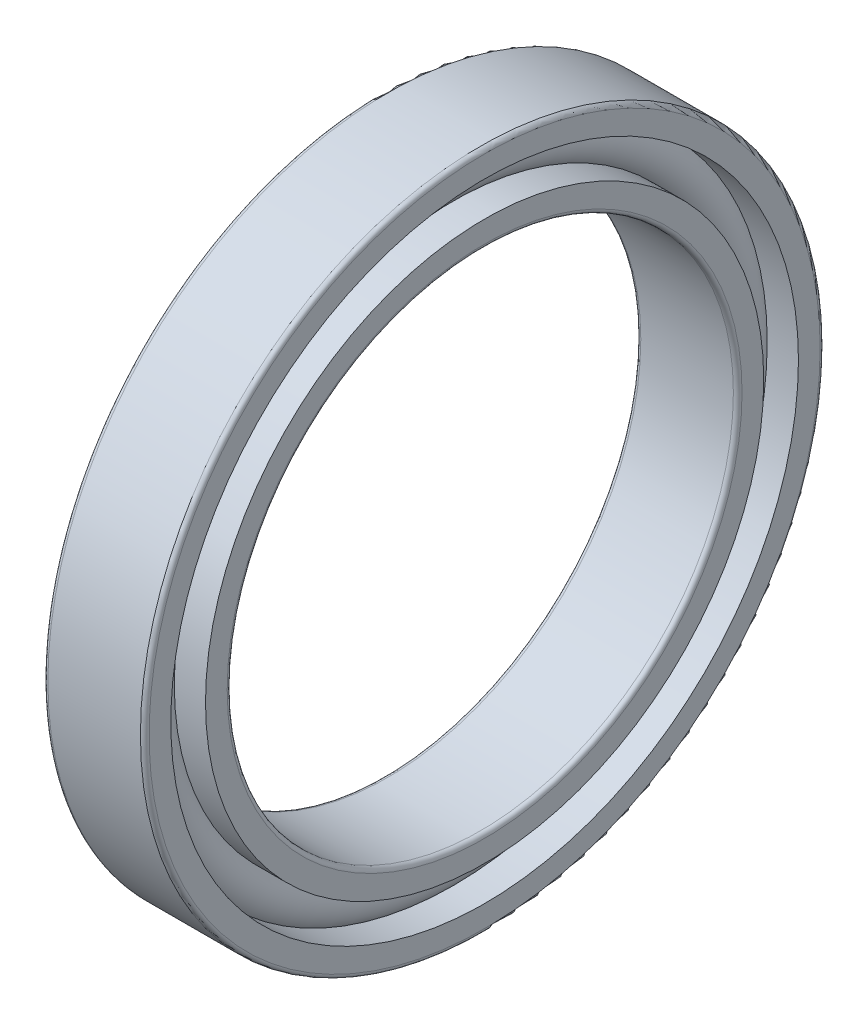
SolidWorks part; units mm, degrees
ref_plane "Plane1" through (0, 0, 0) normal (0, 0, 1) x (1, 0, 0)
ref_plane "Plane2" through (0, 0, 0) normal (0, 1, 0) x (1, 0, 0)
ref_plane "Plane3" through (0, 0, 0) normal (1, 0, 0) x (0, 0, -1)
sketch "Clipboard" plane through (0, 0, 0) normal (0, 0, 1) x (1, 0, 0)
  line L0 (-10, 0) -> (10, 0) construction
  line L1 (0, 0) -> (22.3471, -0.7804)
  line L2 (0, 0) -> (20.4875, 0.7154)
  line L3 (0, 0) -> (22.3471, -0.7804)
  line L4 (0, 0) -> (-22.3573, -0.3902)
  dimension "BallCLRad" = 20.5
sketch "CagSpiSke" plane through (0, 0, 0) normal (0, 0, 1) x (1, 0, 0)
  line L0 (0.18, 20.2) -> (0.18, 20.8)
  line L1 (0.18, 20.8) -> (-0.18, 20.8)
  line L2 (-0.18, 20.8) -> (-0.18, 20.2)
  line L3 (-0.18, 20.2) -> (0.18, 20.2)
  line L4 (-20.6375, 0) -> (20.6375, 0) construction
  line L5 (0, 0) -> (0, 23.7692) construction
  dimension "OD" = 41.6
  dimension "ID" = 40.4
revolve "CageSpine" add sketch "CagSpiSke" angle 0.001 about L4 reverse direction yes
ref_axis "Axis1" through (-50, 0, 0) along (1, 0, 0)
sketch "CagBalSke" plane through (0, 0, 0) normal (0, 0, 1) x (1, 0, 0)
  line L0 (-1.98, 20.5) -> (1.98, 20.5)
  line L1 (-1.905, 20.5) -> (1.905, 20.5) construction
  line L2 (-10, 0) -> (10, 0) construction
  line L3 (0, 0) -> (0, 24) construction
  arc A0 (1.98, 20.5) -> (-1.98, 20.5) centre (0, 20.5) cw
  dimension "BallCLRad" = 20.5
revolve "CageBall" [suppressed] add sketch "CagBalSke" angle 360 about L1 reverse direction yes
pattern_circular "CageBalls" [suppressed] count 2 every 180 about axis through (-50, 0, 0) along (1, 0, 0)
sketch "CagTrmODSke" plane through (0, 0, 0) normal (0, 0, 1) x (1, 0, 0)
  line L0 (1.981, 20.8) -> (1.981, 22.481)
  line L1 (1.981, 22.481) -> (-1.981, 22.481)
  line L2 (-1.981, 22.481) -> (-1.981, 20.8)
  line L3 (-1.981, 20.8) -> (1.981, 20.8)
  line L4 (-20.6375, 0) -> (20.6375, 0) construction
  line L5 (0, 0) -> (0, 25) construction
  dimension "Width" = 3.962
  dimension "ID" = 41.6
  dimension "OD" = 44.962
revolve "CageTrimOD" [suppressed] cut sketch "CagTrmODSke" angle 360 about L4 reverse direction yes
sketch "CagTrmIDSke" plane through (0, 0, 0) normal (0, 0, 1) x (1, 0, 0)
  line L0 (1.981, 18.521) -> (1.981, 20.2)
  line L1 (1.981, 20.2) -> (-1.981, 20.2)
  line L2 (-1.981, 20.2) -> (-1.981, 18.521)
  line L3 (-1.981, 18.521) -> (1.981, 18.521)
  line L4 (-20.6375, 0) -> (20.6375, 0) construction
  line L5 (0, 0) -> (0, 25) construction
  dimension "Width" = 3.962
  dimension "ID" = 37.042
  dimension "OD" = 40.4
revolve "CageTrimID" [suppressed] cut sketch "CagTrmIDSke" angle 360 about L4 reverse direction yes
sketch "BalSimSke" plane through (0, 0, 0) normal (0, 0, 1) x (1, 0, 0)
  line L0 (-10, 0) -> (10, 0) construction
  line L1 (-10, 20.5) -> (10, 20.5) construction
  line L2 (0, 0) -> (0, 23) construction
  circle A0 centre (0, 20.5) radius 1.8
  dimension "BallCLRad" = 20.5
  dimension "Ball_diameter" = 3.6
revolve "BallsSimplified" add sketch "BalSimSke" angle 360 about L0
sketch "BalDetSke" plane through (0, 0, 0) normal (0, 0, 1) x (1, 0, 0)
  line L0 (-1.8, 20.5) -> (1.8, 20.5)
  line L1 (-1.905, 20.5) -> (1.905, 20.5) construction
  line L2 (0, 0) -> (0, 25) construction
  arc A0 (1.8, 20.5) -> (-1.8, 20.5) centre (0, 20.5) cw
  dimension "BallCLRad" = 20.5
  dimension "Ball_diameter" = 3.6
revolve "BallDetailed" [suppressed] add sketch "BalDetSke" angle 360 about L1 reverse direction yes
sketch "InnRacSke" plane through (0, 0, 0) normal (0, 0, 1) x (1, 0, 0)
  line L0 (-1.3079, 19.3) -> (-3.5, 19.3)
  line L1 (-3.5, 19.3) -> (-3.5, 17.8)
  line L2 (-3.2, 17.5) -> (3.2, 17.5)
  line L3 (3.5, 17.8) -> (3.5, 19.3)
  line L4 (3.5, 19.3) -> (1.3079, 19.3)
  line L5 (-20.6375, 0) -> (20.6375, 0) construction
  line L6 (0, 0) -> (0, 30) construction
  arc A0 (-3.5, 17.8) -> (-3.2, 17.5) centre (-3.2, 17.8) ccw
  arc A1 (3.2, 17.5) -> (3.5, 17.8) centre (3.2, 17.8) ccw
  arc A2 (1.3079, 19.3) -> (-1.3079, 19.3) centre (0, 20.5) cw
  dimension "BallCLRad" = 20.5
  dimension "Fillet_radius" = 0.3
  dimension "Ball_diameter" = 3.55
  dimension "ID" = 35
  dimension "OD" = 38.6
  dimension "Width" = 7
revolve "InnerRace" add sketch "InnRacSke" angle 360 about L5 reverse direction yes
sketch "OutRacSke" plane through (0, 0, 0) normal (0, 0, 1) x (1, 0, 0)
  line L0 (-1.3079, 21.7) -> (-3.5, 21.7)
  line L1 (-3.5, 21.7) -> (-3.5, 23.2)
  line L2 (-3.2, 23.5) -> (3.2, 23.5)
  line L3 (3.5, 23.2) -> (3.5, 21.7)
  line L4 (3.5, 21.7) -> (1.3079, 21.7)
  line L5 (-20.6375, 0) -> (20.6375, 0) construction
  line L6 (0, 0) -> (0, 30) construction
  arc A0 (-3.5, 23.2) -> (-3.2, 23.5) centre (-3.2, 23.2) cw
  arc A1 (3.2, 23.5) -> (3.5, 23.2) centre (3.2, 23.2) cw
  arc A2 (1.3079, 21.7) -> (-1.3079, 21.7) centre (0, 20.5) ccw
  dimension "BallCLRad" = 20.5
  dimension "Fillet_radius" = 0.3
  dimension "Ball_diameter" = 3.55
  dimension "Width" = 7
revolve "OuterRace" add sketch "OutRacSke" angle 360 about L5 reverse direction yes
pattern_circular "BallsDetailed" [suppressed] count 2 every 180 about axis through (-50, 0, 0) along (1, 0, 0)
equation "\"BallCLRad@Clipboard\" = ( \"OD@OutRacSke\" + \"ID@InnRacSke\" ) / 4"
equation "\"BallCLRad@BalSimSke\" = \"BallCLRad@Clipboard\""
equation "\"BallCLRad@BalDetSke\" = \"BallCLRad@Clipboard\""
equation "\"BallCLRad@InnRacSke\" = \"BallCLRad@Clipboard\""
equation "\"BallCLRad@OutRacSke\" = \"BallCLRad@Clipboard\""
equation "\"Ball_diameter@InnRacSke\" = \"Ball_diameter@BalDetSke\" - 0.05"
equation "\"Ball_diameter@OutRacSke\" = \"Ball_diameter@BalDetSke\" - 0.05"
equation "\"Ball_diameter@BalSimSke\" = \"Ball_diameter@BalDetSke\""
equation "\"Width@OutRacSke\" = \"Width@InnRacSke\""
equation "\"Fillet_radius@OutRacSke\" = \"Fillet_radius@InnRacSke\""
equation "\"Max_count@Clipboard\" = int( 3.14159265 / atn(( \"Ball_diameter@BalDetSke\" / 2) / sqr( \"BallCLRad@Clipboard\"  *  \"BallCLRad@Clipboard\" - ( \"Ball_diameter@BalDetSke\" / 2) *  ( \"Ball_diameter@BalDetSke\" / 2))))"
equation "\"Max_count@Clipboard\" = ((sgn( \"Max_count@Clipboard\" - \"Count@Clipboard\" )-1)*( \"Max_count@Clipboard\" - \"Count@Clipboard\" ))/-2+ \"Count@Clipboard\""
equation "\"Count@BallsDetailed\" = int( \"Show_count@Clipboard\" ) "
equation "\"Count@BallsDetailed\" = ((sgn( \"Count@BallsDetailed\" - \"Max_count@Clipboard\" )-1)*( \"Count@BallsDetailed\" - \"Max_count@Clipboard\" ))/-2+ \"Max_count@Clipboard\""
equation "\"Count@BallsDetailed\" = ((sgn( \"Count@BallsDetailed\" - \"Min_count@Clipboard\" )+1)*( \"Count@BallsDetailed\" - \"Min_count@Clipboard\"))/2 +\"Min_count@Clipboard\""
equation "\"Angle@BallsDetailed\" = 360.0 / \"Max_count@Clipboard\""
equation "\"BallCLRad@CagBalSke\" = \"BallCLRad@Clipboard\""
equation "\"Count@CageBalls\" = \"Count@BallsDetailed\""
equation "\"Angle@CageBalls\" = \"Angle@BallsDetailed\""
equation "\"Angle@CageSpine\" =  \"Angle@CageBalls\" * ( \"Count@CageBalls\" -1 + int( \"Count@CageBalls\" / \"Max_count@Clipboard\" ) )  + 0.001 -  int( \"Count@CageBalls\" / \"Max_count@Clipboard\" ) * 0.001"
equation "\"Angle@CageSpine\" =  \"Angle@CageSpine\" * int( \"Min_count@Clipboard\" / 2) + int(1 / \"Min_count@Clipboard\")  * 0.001"
equation "\"CageWallOD@CagBalSke\" =  \"Ball_diameter@BalDetSke\" * 1.1"
equation "\"Thickness@CagSpiSke\" =  \"Ball_diameter@BalDetSke\" * 0.1"
equation "\"OD@CagTrmODSke\" = \"BallCLRad@Clipboard\" * 2 + \"CageWallOD@CagBalSke\" + 0.002"
equation "\"ID@CagTrmODSke\" = \"BallCLRad@Clipboard\" * 2 + \"Ball_diameter@BalDetSke\" / 6"
equation "\"OD@CagTrmIDSke\" = \"BallCLRad@Clipboard\" * 2 - \"Ball_diameter@BalDetSke\" / 6"
equation "\"ID@CagTrmIDSke\" = \"BallCLRad@Clipboard\" * 2 - \"CageWallOD@CagBalSke\" + 0.002"
equation "\"OD@CagSpiSke\" = \"ID@CagTrmODSke\""
equation "\"ID@CagSpiSke\" = \"OD@CagTrmIDSke\""
equation "\"Width@CagTrmODSke\" = \"CageWallOD@CagBalSke\" + 0.002"
equation "\"Width@CagTrmIDSke\" = \"CageWallOD@CagBalSke\" + 0.002"
